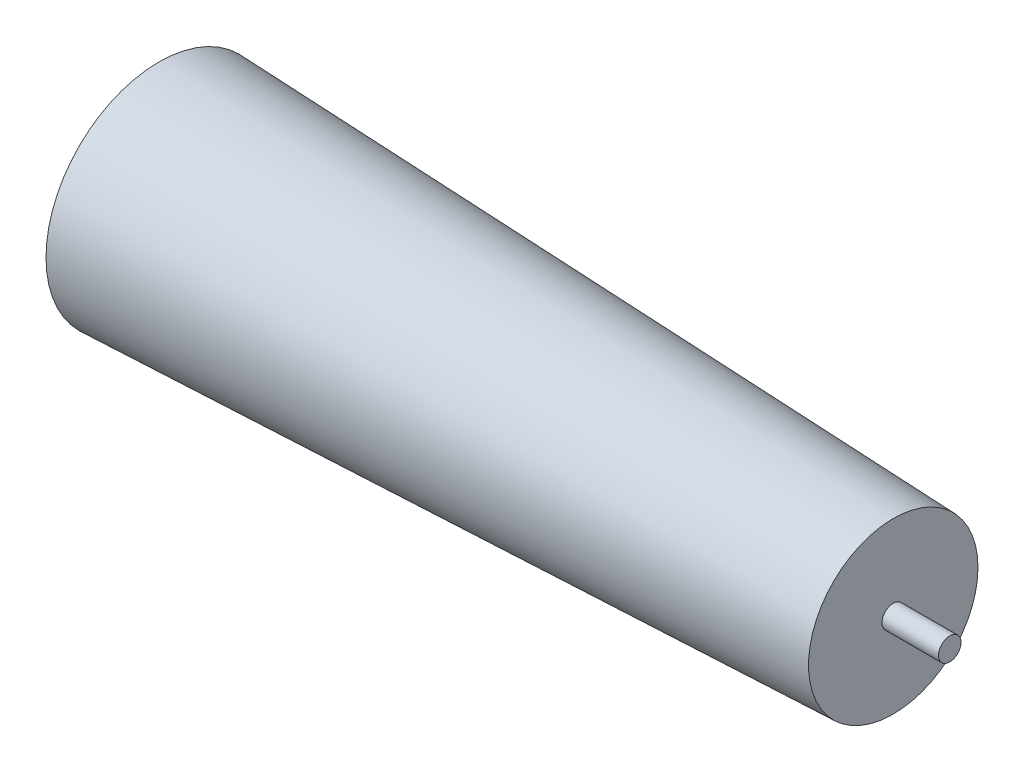
SolidWorks part; units mm, degrees
ref_plane "Front Plane" through (0, 0, 0) normal (0, 0, 1) x (1, 0, 0)
ref_plane "Top Plane" through (0, 0, 0) normal (0, 1, 0) x (1, 0, 0)
ref_plane "Right Plane" through (0, 0, 0) normal (1, 0, 0) x (0, 0, -1)
sketch "Sketch1" plane through (0, 0, 0) normal (1, 0, 0) x (0, 0, -1)
  circle A0 centre (0, 0) radius 40
  dimension "D1" = 80
ref_plane "Plane1" through (260, 0, 0) normal (1, 0, 0) x (0, 0, -1)
sketch "Sketch2" plane through (260, 0, 0) normal (1, 0, 0) x (0, 0, -1)
  circle A0 centre (0, 0) radius 30
  dimension "D1" = 60
loft "Loft1" add profiles "Sketch1", "Sketch2" connector at (0, -12.3752, 38.0375) connector at (260, -12.8416, 27.1126)
sketch "Sketch3" plane through (260, 0, 0) normal (1, 0, 0) x (0, 0, -1)
  circle A0 centre (0, 0) radius 4
  dimension "D1" = 8
extrude "Boss-Extrude1" add sketch "Sketch3" along normal blind 20 and the other way blind 280
